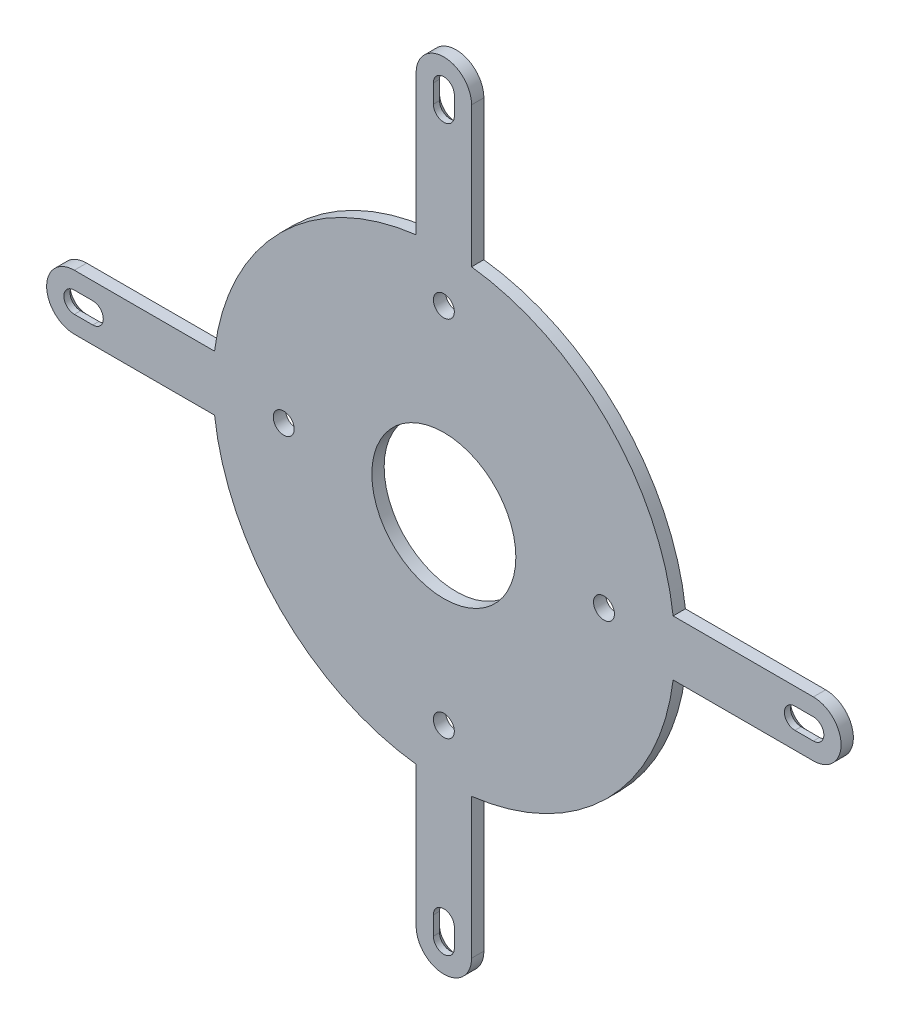
SolidWorks part; units mm, degrees
ref_plane "Front Plane" through (0, 0, 0) normal (0, 0, 1) x (1, 0, 0)
ref_plane "Top Plane" through (0, 0, 0) normal (0, 1, 0) x (1, 0, 0)
ref_plane "Right Plane" through (0, 0, 0) normal (1, 0, 0) x (0, 0, -1)
sketch "Sketch1" plane through (0, 0, 0) normal (0, 0, 1) x (1, 0, 0)
  line L0 (60, 0) -> (-60, 0) construction
  line L1 (60, -4.5) -> (-60, -4.5)
  line L2 (60, 4.5) -> (-60, 4.5)
  line L3 (0, -60) -> (0, 60) construction
  line L4 (-4.5, -60) -> (-4.5, 60)
  line L5 (4.5, -60) -> (4.5, 60)
  line L6 (-60, 0) -> (-57, 0) construction
  line L7 (-60, 1.7) -> (-57, 1.7)
  line L8 (-60, -1.7) -> (-57, -1.7)
  line L9 (0, -60) -> (0, -57) construction
  line L10 (-1.7, -60) -> (-1.7, -57)
  line L11 (1.7, -60) -> (1.7, -57)
  line L12 (60, 0) -> (57, 0) construction
  line L13 (60, -1.7) -> (57, -1.7)
  line L14 (60, 1.7) -> (57, 1.7)
  line L15 (0, 60) -> (0, 57) construction
  line L16 (1.7, 60) -> (1.7, 57)
  line L17 (-1.7, 60) -> (-1.7, 57)
  circle A0 centre (0, 0) radius 37.5
  arc A1 (60, -4.5) -> (60, 4.5) centre (60, 0) ccw
  arc A2 (-60, 4.5) -> (-60, -4.5) centre (-60, 0) ccw
  arc A3 (-4.5, -60) -> (4.5, -60) centre (0, -60) ccw
  arc A4 (4.5, 60) -> (-4.5, 60) centre (0, 60) ccw
  circle A5 centre (0, 29.5) radius 1.7
  circle A6 centre (26, 0) radius 1.7
  circle A7 centre (-26, 0) radius 1.7
  circle A8 centre (0, -29.5) radius 1.7
  arc A13 (-60, 1.7) -> (-60, -1.7) centre (-60, 0) ccw
  arc A14 (-57, -1.7) -> (-57, 1.7) centre (-57, 0) ccw
  arc A15 (-1.7, -60) -> (1.7, -60) centre (0, -60) ccw
  arc A16 (1.7, -57) -> (-1.7, -57) centre (0, -57) ccw
  arc A17 (60, -1.7) -> (60, 1.7) centre (60, 0) ccw
  arc A18 (57, 1.7) -> (57, -1.7) centre (57, 0) ccw
  arc A19 (1.7, 60) -> (-1.7, 60) centre (0, 60) ccw
  arc A20 (-1.7, 57) -> (1.7, 57) centre (0, 57) ccw
  point P5 (0, 0)
  point P11 (0, 0)
  point P31 (-58.5, 0)
  point P36 (0, -58.5)
  point P43 (58.5, 0)
  point P50 (0, 58.5)
  dimension "D1" = 75
  dimension "D3" = 3.4
  dimension "D4" = 4.5
  dimension "D5" = 1.7
  dimension "D2" = 120
  dimension "D6" = 3
extrude "Boss-Extrude1" add sketch "Sketch1" along normal blind 2 contours L2 A2 L1 A0 | L2 A0 L1 L4 A7 | L1 L5 L2 L4 | L5 A0 L4 L2 A5 | L5 A4 L4 A0 | L1 A0 L2 L5 A6 | L1 A1 L2 A0 | L4 A0 L5 L1 A8 | L4 A3 L5 A0 | A0 region at (49.7759, 0, 0) region at (20.7955, 0, 0) region at (0, -20.6848, 0) region at (0, 0, 0) region at (0, -49.7759, 0) region at (-20.7955, 0, 0) region at (0, 20.6848, 0) region at (0, 49.7759, 0) region at (-49.7759, 0, 0)
extrude "Cut-Extrude1" cut sketch "Sketch1<3>" along normal blind 13 contours A7 | A5 | A8 | A6
sketch "Sketch1<3>" plane through (0, 0, 0) normal (0, 0, 1) x (1, 0, 0) same geometry as "Sketch1"
chamfer "Chamfer1" distance 1 angle 45 16 edges at (0, 55.3, 0) (1.7, 58.5, 0) (-1.7, 58.5, 0) (0, 61.7, 0) (-58.5, -1.7, 0) (-61.7, 0, 0) (-55.3, 0, 0) (-58.5, 1.7, 0) (0, -61.7, 0) (1.7, -58.5, 0) (-1.7, -58.5, 0) (0, -55.3, 0) (58.5, -1.7, 0) (61.7, 0, 0) (55.3, 0, 0) (58.5, 1.7, 0)
sketch "Sketch2" plane through (0, 0, 0) normal (0, 0, -1) x (-1, 0, 0)
  circle A0 centre (0, 0) radius 11.6921
extrude "Cut-Extrude2" cut sketch "Sketch2" against normal blind 10
